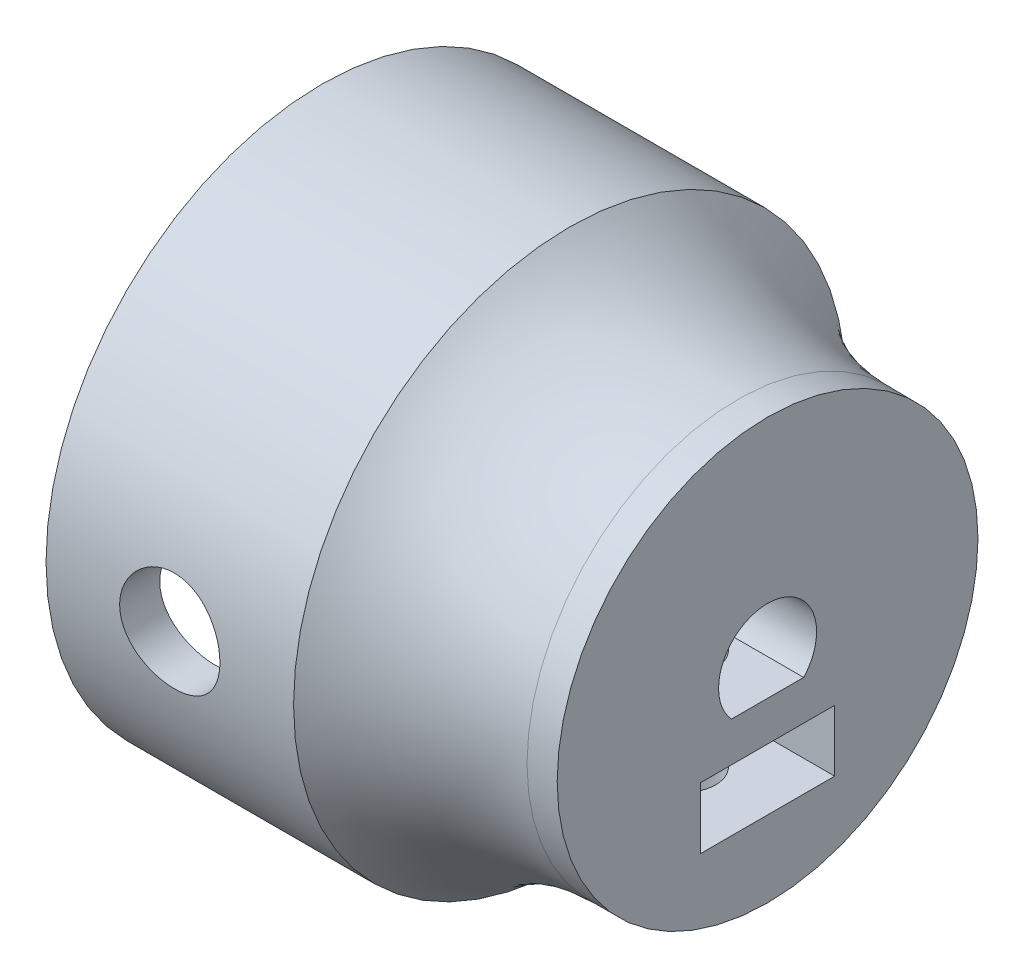
SolidWorks part; units mm, degrees
ref_plane "Alzado" through (0, 0, 0) normal (0, 0, 1) x (1, 0, 0)
ref_plane "Planta" through (0, 0, 0) normal (0, 1, 0) x (1, 0, 0)
ref_plane "Vista lateral" through (0, 0, 0) normal (1, 0, 0) x (0, 0, -1)
sketch "Croquis1" plane through (0, 0, 0) normal (1, 0, 0) x (0, 0, -1)
  line L1 (0, -6.9282) -> (6, -3.4641) construction
  line L2 (6, -3.4641) -> (6, 3.4641) construction
  line L3 (6, 3.4641) -> (0, 6.9282) construction
  line L4 (0, 6.9282) -> (-6, 3.4641) construction
  line L5 (-6, 3.4641) -> (-6, -3.4641) construction
  line L6 (-6, -3.4641) -> (0, -6.9282) construction
  circle A0 centre (0, 0) radius 6.4 construction
  circle A1 centre (0, 0) radius 6 construction
  circle A2 centre (0, 0) radius 8.5
  dimension "D2" = 12.8
  dimension "D3" = 17
  dimension "D1" = 12
extrude "Saliente-Extruir1" add sketch "Croquis1" along normal blind 15
sketch "Croquis2" plane through (15, 0, 0) normal (1, 0, 0) x (0, 0, -1)
  line L0 (-1.4311, -1.28) -> (1.4311, -1.28) construction
  line L7 (0, 0) -> (0, 1.92) construction
  line L8 (-1.4577, -1.34) -> (1.4577, -1.34)
  arc A0 (1.4311, -1.28) -> (-1.4311, -1.28) centre (0, 0) ccw construction
  arc A1 (1.4577, -1.34) -> (-1.4577, -1.34) centre (0, 0) ccw
  dimension "D1" = 3.84
  dimension "D2" = 3.2
  dimension "D3" = 0.06
extrude "Cortar-Extruir1" cut sketch "Croquis2" against normal blind 9
sketch "Croquis9" plane through (0, 0, 0) normal (-1, 0, 0) x (0, 0, 1)
  circle A0 centre (0, 0) radius 11.15
  dimension "D1" = 22.3
extrude "Saliente-Extruir5" add sketch "Croquis9" against normal blind 10
sketch "Croquis3" plane through (0, 0, 0) normal (-1, 0, 0) x (0, 0, 1)
  circle A0 centre (0, 0) radius 9.53
  dimension "D1" = 19.06
extrude "Cortar-Extruir2" cut sketch "Croquis3" against normal blind 9
sketch "Croquis5" plane through (0, 0, 0) normal (0, 0, 1) x (1, 0, 0)
  circle A0 centre (5, 0) radius 2.025
  dimension "D1" = 4.05
  dimension "D2" = 5
extrude "Cortar-Extruir4" cut sketch "Croquis5" against normal through all and the other way through all
sketch "Croquis7" plane through (15, 0, 0) normal (1, 0, 0) x (0, 0, -1)
  line L2 (-1.4577, -1.34) -> (1.4577, -1.34)
  circle A0 centre (0, 0) radius 8.5 construction
  circle A1 centre (0, 0) radius 8.5
  arc A4 (1.4577, -1.34) -> (-1.4577, -1.34) centre (0, 0) ccw
extrude "Saliente-Extruir3" add sketch "Croquis7" along normal blind 3
fillet "Redondeo1" radius 10 1 edges at (10, 0, 8.5)
sketch "Croquis10" plane through (18, 0, 0) normal (1, 0, 0) x (0, 0, -1)
  line L0 (-2.71, -2.94) -> (2.71, -2.94)
  line L1 (-2.65, -3) -> (2.65, -3) construction
  line L2 (-2.65, -3) -> (-2.65, -5.36) construction
  line L3 (-2.65, -5.36) -> (2.65, -5.36) construction
  line L4 (2.65, -3) -> (2.65, -5.36) construction
  line L5 (-2.65, -3) -> (2.65, -5.36) construction
  line L6 (-2.65, -5.36) -> (2.65, -3) construction
  line L7 (2.71, -2.94) -> (2.71, -5.42)
  line L8 (-2.71, -5.42) -> (2.71, -5.42)
  line L9 (-2.71, -2.94) -> (-2.71, -5.42)
  line L11 (-1.4577, -1.34) -> (1.4577, -1.34) construction
  point P4 (0, -4.18)
  point P5 (0, 0)
  dimension "D3" = 0.06
  dimension "D1" = 5.3
  dimension "D2" = 2.36
  dimension "D4" = 1.6
extrude "Cortar-Extruir5" cut sketch "Croquis10" against normal blind 6
sketch "Croquis12" plane through (0, 0, 0) normal (0, 1, 0) x (1, 0, 0)
  line L0 (18, -8.5) -> (18, 8.5) construction
  circle A0 centre (14.65, 0) radius 1.25
  dimension "D1" = 2.5
  dimension "D2" = 3.35
extrude "Cortar-Extruir6" cut sketch "Croquis12" against normal through all
equation "\"D1@Croquis3\"= 19 + \"tolerancia\""
equation "\"tolerancia\"= 0.06"
equation "\"D3@Croquis2\"=\"tolerancia\""
equation "\"D3@Croquis10\"=\"tolerancia\""
